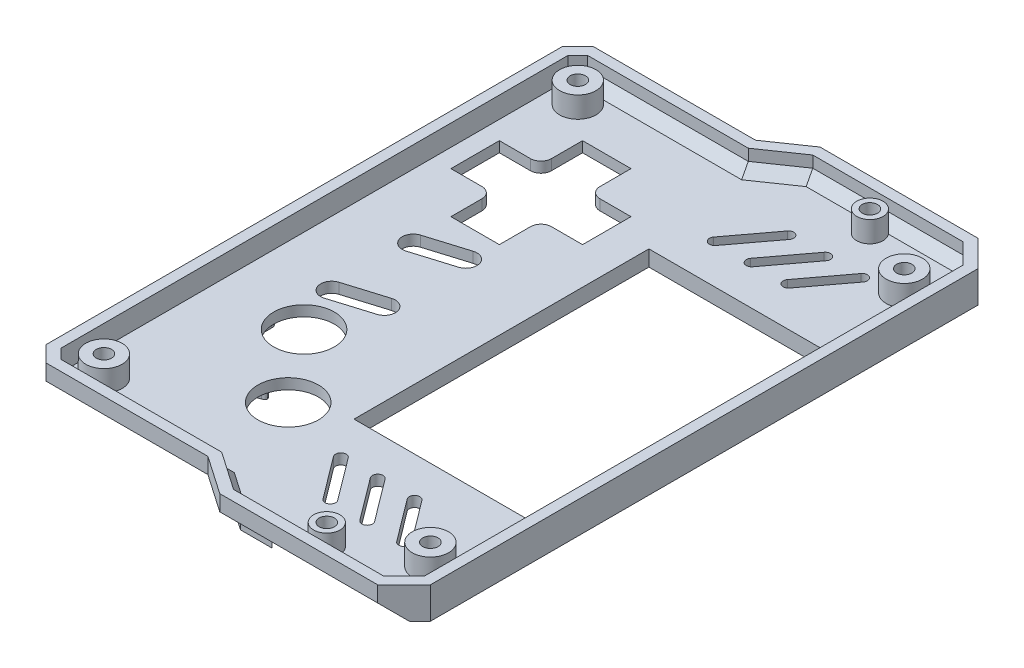
SolidWorks part; units mm, degrees
ref_plane "Front Plane" through (0, 0, 0) normal (0, 0, 1) x (1, 0, 0)
ref_plane "Top Plane" through (0, 0, 0) normal (0, 1, 0) x (1, 0, 0)
ref_plane "Right Plane" through (0, 0, 0) normal (1, 0, 0) x (0, 0, -1)
sketch "Sketch1" plane through (0, 0, 0) normal (0, 1, 0) x (1, 0, 0)
  line L1 (-38, -52) -> (38, -52)
  line L2 (-38, -52) -> (-38, 52)
  line L3 (-38, 52) -> (38, 52)
  line L4 (38, -52) -> (38, 52)
  line L5 (-38, -52) -> (38, 52) construction
  line L6 (-38, 52) -> (38, -52) construction
  point P0 (0, 0)
  dimension "D1" = 104
  dimension "D2" = 76
extrude "Boss-Extrude1" add sketch "Sketch1" along normal blind 9
sketch "Sketch2" plane through (0, 9, 0) normal (0, 1, 0) x (1, 0, 0)
  line L0 (-36, 0) -> (36, 0) construction
  line L1 (36, -50) -> (-36, -50) construction
  line L2 (36, -50) -> (36, 50) construction
  line L3 (36, 50) -> (-36, 50) construction
  line L4 (-36, -50) -> (-36, 50) construction
  line L5 (-23.8252, 6.5805) -> (-16.1748, 8.9195) construction
  line L7 (0, 50) -> (0, -50) construction
  line L8 (-31.5, 27) -> (-8.5, 27) construction
  line L13 (-31.5, 30.6) -> (-23.6, 30.6)
  line L14 (-31.5, 30.6) -> (-31.5, 23.4)
  line L15 (-31.5, 23.4) -> (-23.6, 23.4)
  line L16 (-8.5, 30.6) -> (-8.5, 23.4)
  line L17 (-23.6, 15.5) -> (-16.4, 15.5)
  line L18 (-23.6, 15.5) -> (-23.6, 23.4)
  line L19 (-23.6, 38.5) -> (-16.4, 38.5)
  line L20 (-16.4, 15.5) -> (-16.4, 23.4)
  line L21 (-20, 38.5) -> (-20, 15.5) construction
  line L22 (-23.6, 30.6) -> (-23.6, 38.5)
  line L23 (-16.4, 30.6) -> (-8.5, 30.6)
  line L24 (-16.4, 30.6) -> (-16.4, 38.5)
  line L25 (-16.4, 23.4) -> (-8.5, 23.4)
  line L26 (-24.4392, 8.5888) -> (-16.7888, 10.9277)
  line L27 (-23.2112, 4.5723) -> (-15.5608, 6.9112)
  line L28 (-23.8252, -8.9195) -> (-16.1748, -6.5805) construction
  line L29 (-24.4392, -6.9112) -> (-16.7888, -4.5723)
  line L30 (-23.2112, -10.9277) -> (-15.5608, -8.5888)
  line L32 (34.5, -28) -> (-0.5, -28)
  line L33 (34.5, -28) -> (34.5, 28)
  line L34 (34.5, 28) -> (-0.5, 28)
  line L35 (-0.5, -28) -> (-0.5, 28)
  line L36 (34.5, -28) -> (-0.5, 28) construction
  line L37 (34.5, 28) -> (-0.5, -28) construction
  circle A0 centre (31, 45) radius 1.45
  circle A2 centre (31, -45) radius 1.45
  circle A3 centre (-31, 45) radius 1.45
  circle A4 centre (-31, -45) radius 1.45
  circle A5 centre (-9.5, -31.5) radius 5.75
  circle A6 centre (-20, -18) radius 5.75
  arc A7 (-24.4392, 8.5888) -> (-23.2112, 4.5723) centre (-23.8252, 6.5805) ccw
  arc A8 (-15.5608, 6.9112) -> (-16.7888, 10.9277) centre (-16.1748, 8.9195) ccw
  arc A9 (-24.4392, -6.9112) -> (-23.2112, -10.9277) centre (-23.8252, -8.9195) ccw
  arc A10 (-15.5608, -8.5888) -> (-16.7888, -4.5723) centre (-16.1748, -6.5805) ccw
  point P0 (0, 0)
  point P30 (-20, 27)
  point P32 (-20, 27)
  point P44 (-20, 7.75)
  point P49 (17, 0)
  point P51 (-20, -7.75)
  dimension "D3" = 2.9
  dimension "D6" = 7.2
  dimension "D12" = 11.5
  dimension "D13" = 11.5
  dimension "D18" = 2.1
  dimension "D1" = 100
  dimension "D2" = 72
  dimension "D4" = 5
  dimension "D5" = 67
  dimension "D7" = 7.2
  dimension "D8" = 23
  dimension "D9" = 23
  dimension "D10" = 23
  dimension "D11" = 16
  dimension "D14" = 81.5
  dimension "D15" = 26.5
  dimension "D16" = 16
  dimension "D17" = 32
  dimension "D19" = 8
  dimension "D20" = 107
  dimension "D21" = 16
  dimension "D22" = 42.25
  dimension "D24" = 35
  dimension "D25" = 56
  dimension "D26" = 3
  dimension "D23" = 2
extrude "Cut-Extrude1" cut sketch "Sketch2" against normal through all contours A4 | A2 | A3 | A0
sketch "Sketch3" plane through (0, 0, 0) normal (0, -1, 0) x (1, 0, 0)
  line L0 (-4.25, 52) -> (3, 57)
  line L1 (-38, 52) -> (38, 52) construction
  line L2 (3, 57) -> (33, 57)
  line L3 (33, 57) -> (38, 52)
  line L4 (-4.25, 52) -> (38, 52)
  line L5 (-38, 0) -> (38, 0) construction
  line L6 (-38, -52) -> (-38, 52) construction
  line L7 (38, 52) -> (38, -52) construction
  line L8 (-4.25, -52) -> (3, -57)
  line L9 (3, -57) -> (33, -57)
  line L10 (33, -57) -> (38, -52)
  line L11 (-4.25, -52) -> (38, -52)
  dimension "D1" = 30
  dimension "D2" = 5
  dimension "D3" = 7.25
  dimension "D4" = 5
extrude "Boss-Extrude2" add sketch "Sketch3" against normal through all
chamfer "Chamfer1" distance 3 angle 45 2 edges at (-38, 4.5, 52) (-38, 4.5, -52)
chamfer "Chamfer4" distance 3 angle 45 2 edges at (-19.625, 0, -52) (-19.625, 0, 52)
chamfer "Chamfer5" distance 3 angle 45 4 edges at (18, 0, 57) (18, 0, -57) (-2.8, 0, 53) (-2.8, 0, -53)
shell "Shell2" thickness 2 removed face at (31, 9, -43.55)
extrude "Cut-Extrude4" cut sketch "Sketch2<5>" against normal through all
sketch "Sketch2<5>" plane through (0, 9, 0) normal (0, 1, 0) x (1, 0, 0) same geometry as "Sketch2"
sketch "Sketch4" plane through (0, 0, 0) normal (0, -1, 0) x (1, 0, 0)
  circle A0 centre (-31, -45) radius 1.45 construction
  circle A1 centre (31, -45) radius 1.45 construction
  circle A2 centre (31, 45) radius 1.45 construction
  circle A3 centre (-31, 45) radius 1.45 construction
  circle A4 centre (-31, -45) radius 1.45
  circle A5 centre (31, -45) radius 1.45
  circle A6 centre (31, 45) radius 1.45
  circle A7 centre (-31, 45) radius 1.45
extrude "Boss-Extrude3" add sketch "Sketch4" against normal blind 2
sketch "Sketch5" plane through (0, 0, 0) normal (0, -1, 0) x (1, 0, 0)
  line L0 (-3.3158, 49) -> (3.9342, 54)
  line L1 (3.9342, 54) -> (9.9342, 54)
  line L2 (36, 54) -> (3.9342, 54) construction
  line L3 (9.9342, 54) -> (2.6842, 49)
  line L4 (2.6842, 49) -> (-3.3158, 49)
  dimension "D1" = 6
extrude "Boss-Extrude4" add sketch "Sketch5" along normal blind 1
sketch "Sketch6" plane through (0, 0, 0) normal (0, -1, 0) x (1, 0, 0)
  line L0 (-0.5, 28) -> (34.5, 28) construction
  line L1 (-0.5, 28) -> (34.5, 28)
  line L2 (-0.5, -28) -> (-0.5, 28) construction
  line L3 (-0.5, -28) -> (-0.5, 28)
  line L4 (34.5, -28) -> (-0.5, -28) construction
  line L5 (34.5, -28) -> (-0.5, -28)
  line L6 (34.5, 28) -> (34.5, -28) construction
  line L7 (34.5, 28) -> (34.5, -28)
  line L8 (36.5, 30) -> (36.5, -30)
  line L9 (36.5, -30) -> (-2.5, -30)
  line L10 (-2.5, -30) -> (-2.5, 30)
  line L11 (-2.5, 30) -> (36.5, 30)
  dimension "D1" = 2
extrude "Boss-Extrude5" add sketch "Sketch6" along normal blind 1
sketch "Sketch7" plane through (0, 0, 0) normal (0, -1, 0) x (1, 0, 0)
  line L0 (4.5, 35.5) -> (10.5, 43.5) construction
  line L1 (3.7, 36.1) -> (9.7, 44.1)
  line L2 (5.3, 34.9) -> (11.3, 42.9)
  line L3 (36.5, 30) -> (-2.5, 30) construction
  line L5 (-2.5, 30) -> (-2.5, -30) construction
  line L6 (12.3, 34.9) -> (18.3, 42.9)
  line L7 (10.7, 36.1) -> (16.7, 44.1)
  line L8 (11.5, 35.5) -> (17.5, 43.5) construction
  line L9 (19.3, 34.9) -> (25.3, 42.9)
  line L10 (17.7, 36.1) -> (23.7, 44.1)
  line L11 (18.5, 35.5) -> (24.5, 43.5) construction
  arc A0 (3.7, 36.1) -> (5.3, 34.9) centre (4.5, 35.5) ccw
  arc A1 (11.3, 42.9) -> (9.7, 44.1) centre (10.5, 43.5) ccw
  arc A2 (10.7, 36.1) -> (12.3, 34.9) centre (11.5, 35.5) ccw
  arc A3 (18.3, 42.9) -> (16.7, 44.1) centre (17.5, 43.5) ccw
  arc A4 (17.7, 36.1) -> (19.3, 34.9) centre (18.5, 35.5) ccw
  arc A5 (25.3, 42.9) -> (23.7, 44.1) centre (24.5, 43.5) ccw
  point P2 (7.5, 39.5)
  point P15 (14.5, 39.5)
  point P22 (21.5, 39.5)
  dimension "D1" = 10
  dimension "D2" = 9.5
  dimension "D3" = 10
  dimension "D4" = 3
extrude "Cut-Extrude5" cut sketch "Sketch7" against normal through all
mirror "Mirror1" about plane through (0, 0, 0) normal (0, 0, 1) of "Cut-Extrude5"
sketch "Sketch8" plane through (0, 0, 0) normal (0, -1, 0) x (1, 0, 0)
  text T0 "G.E.M.A.S" font "Arial Rounded MT Bold" height in points 14
extrude "Boss-Extrude6" add sketch "Sketch8" along normal blind 1
sketch "Sketch10" plane through (0, 0, 0) normal (0, -1, 0) x (1, 0, 0)
  line L0 (-18.1571, 34.362) -> (-18.1571, 25.5881) construction
  line L1 (-29.3649, 22.2385) -> (-29.3649, 13.8955) construction
  line L2 (-11.6822, 15.2995) -> (-11.6822, 0) construction
  line L3 (-11.6822, -0.6966) -> (-11.6822, -13.9073) construction
  text T0 "A" font "Arial Rounded MT Bold" height 3.175
  text T1 "B" font "Arial Rounded MT Bold" height 3.175
  text T2 "START" font "Arial Rounded MT Bold" height in points 10
  text T3 "SELECT" font "Arial Rounded MT Bold" height in points 10
extrude "Boss-Extrude7" add sketch "Sketch10" along normal blind 1
mirror "Mirror4" about plane through (0, 0, 0) normal (0, 0, 1) of "Boss-Extrude4"
sketch "Sketch11" plane through (0, 2, 0) normal (0, 1, 0) x (1, 0, 0)
  line L0 (-16.4, 30.6) -> (-8.5, 30.6) construction
  line L1 (-16.4, 30.6) -> (-8.5, 30.6)
  line L2 (-32.5, 22.4) -> (-24.6, 22.4)
  line L3 (-24.6, 22.4) -> (-24.6, 14.5)
  line L4 (-24.6, 14.5) -> (-15.4, 14.5)
  line L5 (-15.4, 14.5) -> (-15.4, 22.4)
  line L6 (-15.4, 22.4) -> (-7.5, 22.4)
  line L7 (-7.5, 22.4) -> (-7.5, 31.6)
  line L8 (-7.5, 31.6) -> (-15.4, 31.6)
  line L9 (-15.4, 31.6) -> (-15.4, 39.5)
  line L10 (-15.4, 39.5) -> (-24.6, 39.5)
  line L11 (-24.6, 39.5) -> (-24.6, 31.6)
  line L12 (-24.6, 31.6) -> (-32.5, 31.6)
  line L13 (-32.5, 31.6) -> (-32.5, 22.4)
  line L14 (-31.5, 23.4) -> (-23.6, 23.4)
  line L15 (-31.5, 30.6) -> (-31.5, 23.4)
  line L16 (-23.6, 30.6) -> (-31.5, 30.6)
  line L17 (-23.6, 38.5) -> (-23.6, 30.6)
  line L18 (-16.4, 38.5) -> (-23.6, 38.5)
  line L19 (-16.4, 30.6) -> (-16.4, 38.5)
  line L20 (-8.5, 30.6) -> (-16.4, 30.6)
  line L21 (-8.5, 23.4) -> (-8.5, 30.6)
  line L22 (-16.4, 23.4) -> (-8.5, 23.4)
  line L23 (-16.4, 15.5) -> (-16.4, 23.4)
  line L24 (-23.6, 15.5) -> (-16.4, 15.5)
  line L25 (-23.6, 23.4) -> (-23.6, 15.5)
  line L26 (-31.5, 23.4) -> (-23.6, 23.4)
  line L27 (-31.5, 30.6) -> (-31.5, 23.4)
  line L28 (-23.6, 30.6) -> (-31.5, 30.6)
  line L29 (-23.6, 38.5) -> (-23.6, 30.6)
  line L30 (-16.4, 38.5) -> (-23.6, 38.5)
  line L31 (-16.4, 30.6) -> (-16.4, 38.5)
  line L32 (-8.5, 30.6) -> (-16.4, 30.6)
  line L33 (-8.5, 23.4) -> (-8.5, 30.6)
  line L34 (-16.4, 23.4) -> (-8.5, 23.4)
  line L35 (-16.4, 15.5) -> (-16.4, 23.4)
  line L36 (-23.6, 15.5) -> (-16.4, 15.5)
  line L37 (-23.6, 23.4) -> (-23.6, 15.5)
  dimension "D1" = 0
  dimension "D2" = 1
extrude "Cut-Extrude6" cut sketch "Sketch11" against normal through all contours L12 L13 L2 L3 L4 L5 L6 L7 L8 L9 L10 L11 L37 L26 L27 L28 L29 L30 L31 L1 L33 L34 L35 L36 region at (-32.1464, 2, -27)
fillet "Fillet1" radius 2 4 edges at (-15.4, 1, -31.6) (-15.4, 1, -22.4) (-24.6, 1, -31.6) (-24.6, 1, -22.4)
sketch "Sketch12" plane through (0, 9, 0) normal (0, 1, 0) x (1, 0, 0)
  line L12 (-38, 49) -> (-38, -49)
  line L13 (-38, -49) -> (-35, -52)
  line L14 (-35, -52) -> (-4.25, -52)
  line L15 (-4.25, -52) -> (3, -57)
  line L16 (3, -57) -> (33, -57)
  line L17 (33, -57) -> (38, -52)
  line L18 (38, -52) -> (38, 52)
  line L19 (38, 52) -> (33, 57)
  line L20 (33, 57) -> (3, 57)
  line L21 (3, 57) -> (-4.25, 52)
  line L22 (-4.25, 52) -> (-35, 52)
  line L23 (-35, 52) -> (-38, 49)
  line L24 (-38, 49) -> (-38, -49)
  line L25 (-38, -49) -> (-35, -52)
  line L26 (-35, -52) -> (-4.25, -52)
  line L27 (-4.25, -52) -> (3, -57)
  line L28 (3, -57) -> (33, -57)
  line L29 (33, -57) -> (38, -52)
  line L30 (38, -52) -> (38, 52)
  line L31 (38, 52) -> (33, 57)
  line L32 (33, 57) -> (3, 57)
  line L33 (3, 57) -> (-4.25, 52)
  line L34 (-4.25, 52) -> (-35, 52)
  line L35 (-35, 52) -> (-38, 49)
  dimension "D1" = 0
extrude "Cut-Extrude7" cut sketch "Sketch12" against normal blind 3
sketch "Sketch13" plane through (0, 2, 0) normal (0, 1, 0) x (1, 0, 0)
  line L0 (32.1716, -55) -> (3.6228, -55) construction
  line L1 (34, -53.1716) -> (4.1921, -53.1716) construction
  circle A0 centre (17.8972, -51.5716) radius 1.45
  circle A1 centre (17.8972, -51.5716) radius 2.5
  point P3 (18.6758, -52.3391)
  point P6 (17.8972, -55)
  dimension "D1" = 2.9
  dimension "D2" = 5
  dimension "D3" = 1.6
extrude "Boss-Extrude8" add sketch "Sketch13" along normal up to surface (4 mm away) up to face at (31, 6, 46.45)
mirror "Mirror5" about plane through (0, 0, 0) normal (0, 0, 1) of "Boss-Extrude8"
